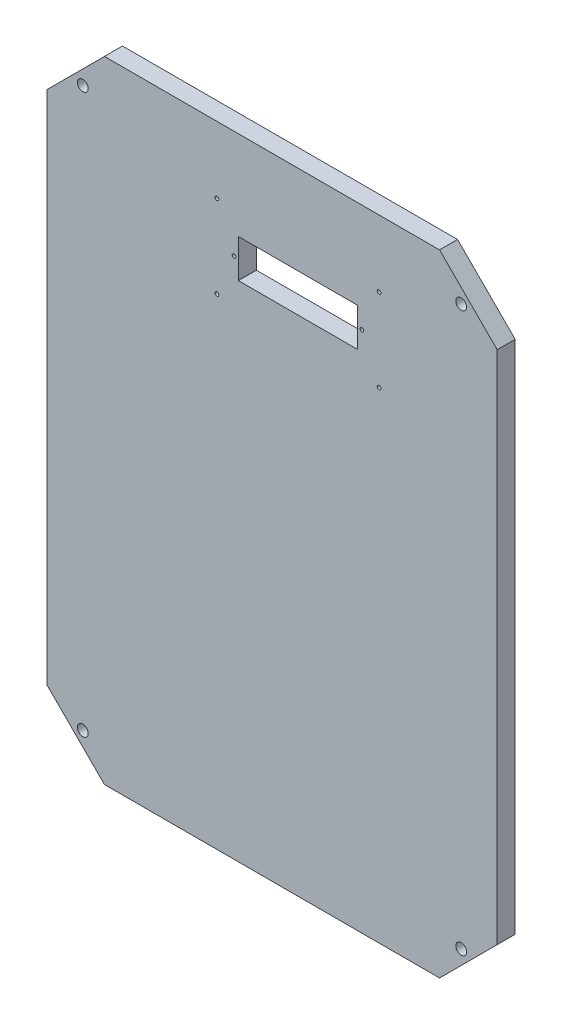
SolidWorks part; units mm, degrees
ref_plane "Plan de face" through (0, 0, 0) normal (0, 0, 1) x (1, 0, 0)
ref_plane "Plan de dessus" through (0, 0, 0) normal (0, 1, 0) x (1, 0, 0)
ref_plane "Plan de droite" through (0, 0, 0) normal (1, 0, 0) x (0, 0, -1)
sketch "Esquisse1" plane through (0, 0, 0) normal (0, 0, 1) x (1, 0, 0)
  line L0 (893.1688, 495.1101) -> (925.1688, 527.1101)
  line L1 (707.1688, 495.1101) -> (893.1688, 495.1101)
  line L2 (675.1688, 527.1101) -> (707.1688, 495.1101)
  line L3 (675.1688, 813.1101) -> (675.1688, 527.1101)
  line L4 (707.1688, 845.1101) -> (675.1688, 813.1101)
  line L5 (893.1688, 845.1101) -> (707.1688, 845.1101)
  line L6 (925.1688, 813.1101) -> (893.1688, 845.1101)
  line L7 (925.1688, 527.1101) -> (925.1688, 813.1101)
  line L8 (814.6014, 803.1101) -> (814.6014, 767.1101) construction
  line L9 (854.6014, 803.1101) -> (774.6014, 803.1101) construction
  line L10 (854.6014, 803.1101) -> (854.6014, 767.1101) construction
  line L11 (854.6014, 767.1101) -> (774.6014, 767.1101) construction
  line L12 (774.6014, 803.1101) -> (774.6014, 767.1101) construction
  line L13 (774.6014, 785.1101) -> (854.6014, 785.1101) construction
  line L14 (800.1688, 845.1101) -> (800.1688, 495.1101) construction
  line L15 (847.7014, 795.7101) -> (781.5014, 795.7101)
  line L16 (847.7014, 795.7101) -> (847.7014, 774.5101)
  line L17 (847.7014, 774.5101) -> (781.5014, 774.5101)
  line L18 (781.5014, 795.7101) -> (781.5014, 774.5101)
  line L19 (847.7014, 795.7101) -> (781.5014, 774.5101) construction
  line L20 (847.7014, 774.5101) -> (781.5014, 795.7101) construction
  line L21 (675.1688, 670.1101) -> (925.1688, 670.1101) construction
  circle A0 centre (695.1688, 515.1101) radius 3
  circle A1 centre (695.1688, 825.1101) radius 3
  circle A2 centre (905.1688, 825.1101) radius 3
  circle A3 centre (905.1688, 515.1101) radius 3
  circle A4 centre (859.6014, 808.1101) radius 1.05
  circle A5 centre (769.6014, 808.1101) radius 1.05
  circle A6 centre (769.6014, 762.1101) radius 1.05
  circle A7 centre (859.6014, 762.1101) radius 1.05
  circle A8 centre (850.1014, 785.1101) radius 1
  circle A9 centre (779.1014, 785.1101) radius 1
  point P32 (814.6014, 785.1101)
  dimension "D4" = 2.1
  dimension "D9" = 2
  dimension "D17" = 20
  dimension "D18" = 20
  dimension "D1" = 310
  dimension "D2" = 80
  dimension "D3" = 36
  dimension "D5" = 5
  dimension "D6" = 5
  dimension "D7" = 66.2
  dimension "D8" = 21.2
  dimension "D10" = 35.5
  dimension "D11" = 20
  dimension "D12" = 20
  dimension "D13" = 20
  dimension "D14" = 20
  dimension "D15" = 20
  dimension "D16" = 20
extrude "Boss.-Extru.1" add sketch "Esquisse1" along normal blind 10
